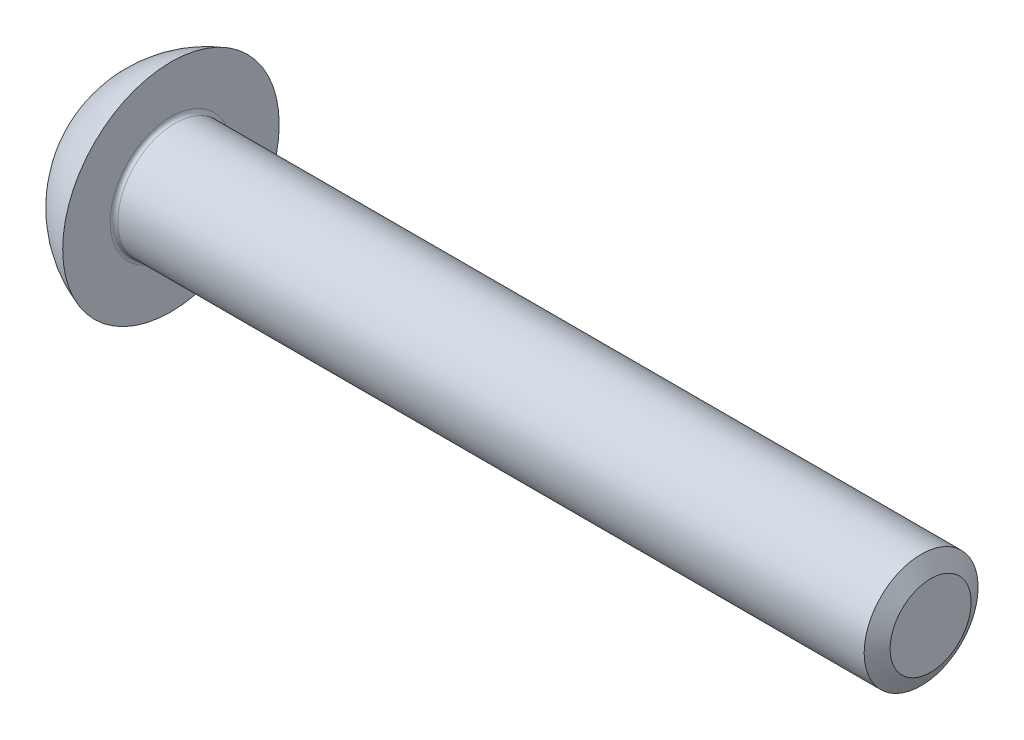
SolidWorks part; units mm, degrees
ref_plane "前视基准面" through (0, 0, 0) normal (0, 0, 1) x (1, 0, 0)
ref_plane "上视基准面" through (0, 0, 0) normal (0, 1, 0) x (1, 0, 0)
ref_plane "右视基准面" through (0, 0, 0) normal (1, 0, 0) x (0, 0, -1)
sketch "尺寸草图" plane through (0, 0, 0) normal (0, 0, 1) x (1, 0, 0)
  line L0 (0, 0) -> (20, 0) construction
  line L1 (20, 0) -> (20, 1.5) construction
  line L2 (20, 1.5) -> (19.5, 1.5) construction
  line L3 (0, 0) -> (0, 2.85) construction
  point P3 (1, 0)
  point P6 (20, 1.8)
  point P7 (0, 0.55)
  point P9 (1.65, 0)
  point P10 (1.75, 0)
  point P11 (20, 1)
  point P12 (2.79, 0)
  point P13 (2.99, 0)
  point P14 (20, 21.8)
  dimension "l" = 20
  dimension "d" = 3
  dimension "P" = 0.5
  dimension "a" = 1
  dimension "da" = 3.6
  dimension "dk" = 5.7
  dimension "e" = 2.3
  dimension "K" = 1.65
  dimension "r" = 0.1
  dimension "s" = 2
  dimension "t" = 1.04
  dimension "w" = 0.2
  dimension "zslwx" = 20
sketch "草图1" plane through (0, 0, 0) normal (0, 0, 1) x (1, 0, 0)
  line L0 (-21.65, 0) -> (0, 0) construction
  line L1 (0, 1.5) -> (-19.9, 1.5)
  line L2 (-20, 1.6) -> (-20, 2.85)
  line L3 (-21.65, 0) -> (-21.65, 1.5)
  line L4 (0, 1.5) -> (0, 0)
  line L5 (-21.65, 0) -> (0, 0)
  arc A0 (-20, 2.85) -> (-21.65, 1.5) centre (-19.0455, 0) ccw
  arc A1 (-19.9, 1.5) -> (-20, 1.6) centre (-19.9, 1.6) cw
  point P10 (-20, 1.5)
  dimension "r" = 0.1
  dimension "d" = 3
  dimension "dk" = 5.7
  dimension "k" = 1.65
  dimension "l" = 20
revolve "旋转1" add sketch "草图1" angle 360 about L0
cosmetic thread "装饰螺纹线1" parameters "D1"=20, "D2"=2.58
sketch "草图2" plane through (-21.65, 0, 0) normal (-1, 0, 0) x (0, 0, 1)
  line L1 (0, 1.1547) -> (-1, 0.5774)
  line L2 (-1, 0.5774) -> (-1, -0.5774)
  line L3 (-1, -0.5774) -> (0, -1.1547)
  line L4 (0, -1.1547) -> (1, -0.5774)
  line L5 (1, -0.5774) -> (1, 0.5774)
  line L6 (1, 0.5774) -> (0, 1.1547)
  circle A0 centre (0, 0) radius 1 construction
  dimension "s" = 2
extrude "切除-拉伸1" cut sketch "草图2" against normal blind 1.65
sketch "草图6" plane through (0, 0, 0) normal (0, 0, 1) x (1, 0, 0)
  line L0 (-20.61, 1.1547) -> (-20, 0)
  line L1 (-19.7, 1.1547) -> (-19.7, 0)
  line L2 (-19.7, 1.1547) -> (-20.61, 1.1547)
  line L3 (-21.65, 0) -> (-20, 0) construction
  line L4 (-19.7, 0) -> (-20, 0)
  line L5 (-21.65, 0) -> (-23.95, 0) construction
  dimension "t" = 1.04
  dimension "e-s" = 0.3
  dimension "k" = 1.65
  dimension "e" = 2.3
revolve "旋转2" add sketch "草图6" angle 360 about L3
sketch "草图7" plane through (0, 0, 0) normal (0, 0, 1) x (1, 0, 0)
  line L3 (-21.65, 1.1547) -> (-21.35, 0)
  line L4 (-21.65, 0) -> (-21.35, 0) construction
  line L7 (-21.65, 1.1547) -> (-21.65, 0)
  line L8 (-21.65, 0) -> (-21.35, 0)
  dimension "e-s" = 0.3
revolve "切除-旋转5" cut sketch "草图7" angle 360 about L4
sketch "草图4" plane through (0, 0, 0) normal (0, 0, 1) x (1, 0, 0)
  line L0 (-0.25, 1.5) -> (0, 1.067)
  line L1 (-0.25, 1.5) -> (0.25, 1.5)
  line L2 (0.25, 1.5) -> (0, 1.067)
  line L4 (0, -1.5) -> (0, 1.5) construction
  line L5 (-0.25, 0) -> (0.25, 0) construction
  dimension "d" = 1.5
  dimension "p" = 0.5
revolve "切除-旋转1" cut sketch "草图4" angle 360 about L5
ref_axis "基准轴1" through (-8.1887, 0, 0) along (1, 0, 0)
pattern_linear "阵列(线性)1" [suppressed] count 38 spacing 0.5 along (-1, 0, 0) of bodies 104
